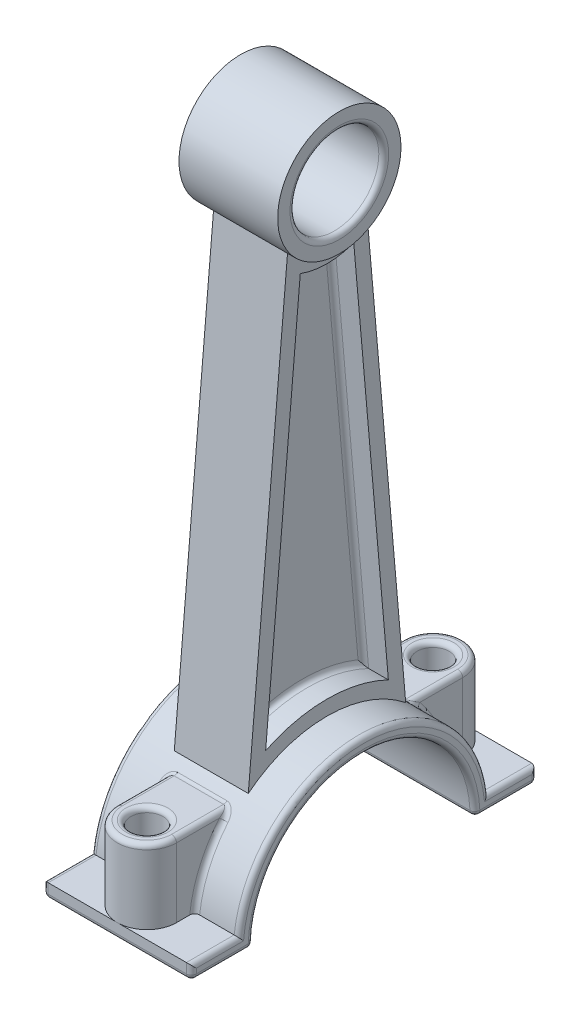
SolidWorks part; units mm, degrees
ref_plane "Front Plane" through (0, 0, 0) normal (0, 0, 1) x (1, 0, 0)
ref_plane "Top Plane" through (0, 0, 0) normal (0, 1, 0) x (1, 0, 0)
ref_plane "Right Plane" through (0, 0, 0) normal (1, 0, 0) x (0, 0, -1)
sketch "Sketch1" plane through (0, 0, 0) normal (1, 0, 0) x (0, 0, -1)
  line L0 (0, 0) -> (0, -120.4) construction
  line L1 (22.5, -120.4) -> (35, -120.4)
  line L2 (-22.5, -120.4) -> (-35, -120.4)
  line L3 (25.3229, -117.4) -> (35, -117.4)
  line L4 (-25.3229, -117.4) -> (-35, -117.4)
  line L5 (-35, -117.4) -> (-35, -120.4)
  line L6 (35, -117.4) -> (35, -120.4)
  line L7 (-8, -9.6047) -> (-15.9529, -100.5064)
  line L8 (8, -9.6047) -> (15.9529, -100.5064)
  circle A0 centre (0, 0) radius 12.5
  circle A1 centre (0, 0) radius 9
  arc A2 (22.5, -120.4) -> (-22.5, -120.4) centre (0, -120.4) ccw
  arc A3 (25.3229, -117.4) -> (-25.3229, -117.4) centre (0, -120.4) ccw
  dimension "D1" = 25
  dimension "D2" = 18
  dimension "D3" = 45
  dimension "D4" = 120.4
  dimension "D5" = 35
  dimension "D7" = 8
  dimension "D8" = 5
  dimension "D6" = 3
extrude "Boss-Extrude1" add sketch "Sketch1" along normal mid plane 20 contours A1 A0 region at (0, -12.1464, 0)
extrude "Boss-Extrude2" add sketch "Sketch1<3>" along normal mid plane 30 separate body contours A2 L2 L5 L4 A3 L3 L6 L1
sketch "Sketch1<3>" plane through (0, 0, 0) normal (1, 0, 0) x (0, 0, -1) same geometry as "Sketch1"
extrude "Boss-Extrude3" add sketch "Sketch1<4>" along normal mid plane 15 contours L0 A0 L7 A3 | A0 L0 A3 L8 region at (0, -58.5545, -6.2653) region at (0, -58.5545, 6.2653)
sketch "Sketch1<4>" plane through (0, 0, 0) normal (1, 0, 0) x (0, 0, -1) same geometry as "Sketch1"
sketch "Sketch2" plane through (0, -117.4, 0) normal (0, 1, 0) x (1, 0, 0)
  line L0 (0, 35) -> (0, 19.3619) construction
  line L1 (15, 35) -> (-15, 35) construction
  line L3 (-4.7179, 35) -> (4.7179, 35)
  line L4 (-6, 29) -> (-6, 17)
  line L5 (-6, 17) -> (6, 17)
  line L6 (6, 29) -> (6, 17)
  arc A0 (6, 29) -> (-6, 29) centre (0, 29) ccw
  line M9 (-15, 25.3229) -> (15, 25.3229)
  dimension "D1" = 6
  dimension "D2" = 12
extrude "Boss-Extrude5" add sketch "Sketch2" along normal blind 15 contours A0 L0 L6 M9 | A0 L4 L5 L6 region at (2.7453, -117.4, -29.6245)
sketch "Sketch3" plane through (0, -102.4, 0) normal (0, 1, 0) x (1, 0, 0)
  circle A0 centre (0, 29) radius 3.25
  dimension "D1" = 6.5
extrude "Cut-Extrude1" cut sketch "Sketch3" against normal through all
mirror "Mirror1" about plane through (0, 0, 0) normal (0, 0, 1) of "Cut-Extrude1", "Boss-Extrude5"
sketch "Sketch4" plane through (15, 0, 0) normal (1, 0, 0) x (0, 0, -1)
  line L0 (-22.5, -120.4) -> (22.5, -120.4)
  arc A0 (22.5, -120.4) -> (-22.5, -120.4) centre (0, -120.4) ccw construction
  arc A1 (22.5, -120.4) -> (-22.5, -120.4) centre (0, -120.4) ccw
extrude "Cut-Extrude2" cut sketch "Sketch4" against normal through all
sketch "Sketch5" plane through (7.5, 0, 0) normal (1, 0, 0) x (0, 0, -1)
  line L0 (-5.4187, -14.522) -> (-12.4385, -94.7576)
  line L1 (12.4385, -94.7576) -> (5.4187, -14.522)
  line L2 (15.9529, -100.5064) -> (8, -9.6047)
  line L3 (-8, -9.6047) -> (-15.9529, -100.5064)
  line L4 (15.9529, -100.5064) -> (8, -9.6047)
  line L5 (-8, -9.6047) -> (-15.9529, -100.5064)
  arc A0 (12.4385, -94.7576) -> (-12.4385, -94.7576) centre (0, -120.4) ccw
  arc A1 (-5.4187, -14.522) -> (5.4187, -14.522) centre (0, 0) ccw
  arc A2 (15.9529, -100.5064) -> (-15.9529, -100.5064) centre (0, -120.4) ccw
  arc A3 (-8, -9.6047) -> (8, -9.6047) centre (0, 0) ccw
  arc A4 (15.9529, -100.5064) -> (-15.9529, -100.5064) centre (0, -120.4) ccw
  arc A5 (-8, -9.6047) -> (8, -9.6047) centre (0, 0) ccw
  dimension "D1" = 0
  dimension "D2" = 3
extrude "Cut-Extrude4" cut sketch "Sketch5" against normal blind 5 contours A1 L0 A0 L1 region at (7.5, -58.957, 0)
mirror "Mirror3" about plane through (0, 0, 0) normal (1, 0, 0) of "Cut-Extrude4"
fillet "Fillet1" radius 1 45 edges at (-6, -109.2901, -22.9526) (6, -109.2901, -22.9526) (6, -109.2901, 22.9526) (-6, -109.2901, 22.9526) (-6, -102.4, -23.5312) (0, -102.4, -35) (6, -102.4, -23.5312) (0, -102.4, -18.0624) (0, -120.4, -22.5) (0, -120.4, -35) (0, -120.4, -25.75) (0, -120.4, 35) (0, -120.4, 22.5) (0, -120.4, 25.75) (-15, -118.9, -35) (-15, -117.4, -30.1615) (-15, -94.9, 0) (-15, -117.4, 30.1615) (-15, -118.9, 35) (-15, -120.4, 28.75) (-15, -97.9, 0) (-15, -120.4, -28.75) (15, -97.9, 0) (15, -120.4, 28.75) (15, -118.9, 35) (15, -117.4, 30.1615) (15, -94.9, 0) (15, -117.4, -30.1615) (15, -118.9, -35) (15, -120.4, -28.75) (6, -102.4, 23.5312) (0, -102.4, 35) (-6, -102.4, 23.5312) (0, -102.4, 18.0624) (0, -102.4, 25.75) (-2.5, -54.6398, 8.9286) (-2.5, -91.9, 0) (-2.5, -54.6398, -8.9286) (-2.5, -15.5, 0) (2.5, -54.6398, -8.9286) (2.5, -91.9, 0) (2.5, -54.6398, 8.9286) (2.5, -15.5, 0) (-10, 0, -9) (10, 0, -9)
fillet "Fillet2" radius 1 1 edges at (0, -102.4, -25.75)
